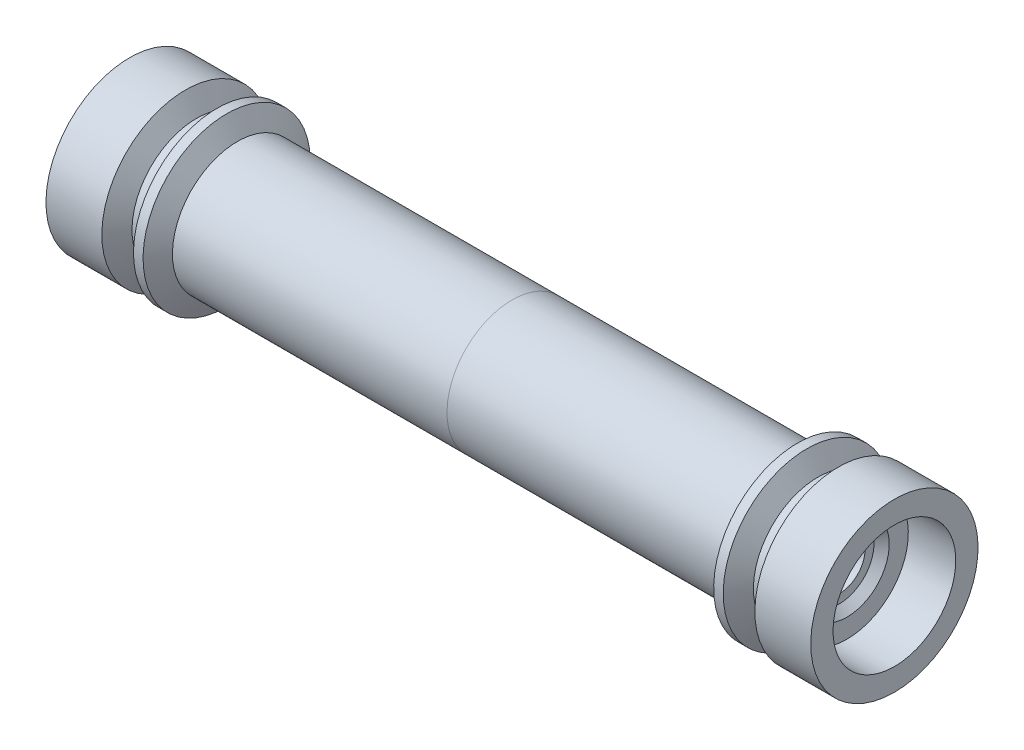
SolidWorks part; units mm, degrees
ref_plane "Front Plane" through (0, 0, 0) normal (0, 0, 1) x (1, 0, 0)
ref_plane "Top Plane" through (0, 0, 0) normal (0, 1, 0) x (1, 0, 0)
ref_plane "Right Plane" through (0, 0, 0) normal (1, 0, 0) x (0, 0, -1)
sketch "Sketch2" plane through (0, 0, 0) normal (0, 0, 1) x (1, 0, 0)
  line L0 (0, 0) -> (0, 28.4375) construction
  line L1 (-25.4, 4.075) -> (-22.25, 4.075) construction
  line L2 (-25.4, 4.075) -> (-25.4, -4.075) construction
  line L3 (-25.4, -4.075) -> (-22.25, -4.075) construction
  line L4 (-22.25, 4.075) -> (-22.25, -4.075) construction
  line L5 (-25.4, 4.075) -> (-22.25, -4.075) construction
  line L6 (-25.4, -4.075) -> (-22.25, 4.075) construction
  line L7 (22.25, 4.5) -> (41.3332, 4.5) construction
  line L8 (22.25, 4.5) -> (22.25, -4.5) construction
  line L9 (22.25, -4.5) -> (41.3332, -4.5) construction
  line L10 (41.3332, 4.5) -> (41.3332, -4.5) construction
  line L11 (22.25, 4.5) -> (41.3332, -4.5) construction
  line L12 (22.25, -4.5) -> (41.3332, 4.5) construction
  line L13 (-25.4, 0) -> (41.3332, 0) construction
  line L14 (-25.4, 5.5562) -> (-21.6882, 5.5562)
  line L21 (-18.2369, 4.318) -> (0, 4.318)
  line L22 (-25.4, 5.5562) -> (-25.4, 4.075)
  line L23 (-25.4, 4.075) -> (-22.25, 4.075)
  line L24 (-22.25, 4.075) -> (-22.25, 0)
  line L25 (-22.25, 0) -> (0, 0)
  line L26 (0, 0) -> (0, 4.318)
  line L27 (-30.6688, -5.5562) -> (-30.6688, 5.5562) construction
  line L28 (-21.6882, 5.5562) -> (-20.955, 4.2862)
  line L29 (-20.955, 4.2862) -> (-20.32, 4.2862)
  line L30 (-25.4, 5.5562) -> (25.4, 5.5562) construction
  line L31 (0, 1.6) -> (-12.5, 1.6)
  line L32 (-12.5, 1.6) -> (-14.1, 0)
  line L33 (-12.5, 1.6) -> (-12.5, -1.6) construction
  line L34 (-12.5, 1.6) -> (12.5, 1.6) construction
  line L35 (-22.25, 1.7145) -> (-15.575, 1.7145)
  line L36 (-15.575, 1.7145) -> (-15.575, 0)
  line L37 (-22.25, 2.805) -> (-21.742, 2.297)
  line L38 (-15.575, 1.7145) -> (-28.575, 1.7145) construction
  line L39 (-15.575, 1.7145) -> (-15.575, -1.7145) construction
  line L40 (-15.575, -1.7145) -> (-28.575, -1.7145) construction
  line L41 (-28.575, 1.7145) -> (-28.575, -1.7145) construction
  line L42 (-21.742, 2.297) -> (-21.742, 0)
  line L46 (-20.32, 4.2862) -> (-19.5868, 5.5562)
  line L47 (-19.5868, 5.5562) -> (-18.9518, 5.5562)
  line L48 (-18.9518, 5.5562) -> (-18.2369, 4.318)
  line L49 (-20.6375, 4.2862) -> (-20.6375, 8.7882) construction
  line L50 (-20.6375, 8.7882) -> (20.6375, 8.7882) construction
  point P0 (-23.825, 0)
  point P5 (31.7916, 0)
  point P27 (-30.6688, 0)
  point P29 (-12.5, 0)
  point P33 (0, 8.7882)
  point P36 (0, 1.6)
  point P48 (-15.575, 0)
  point P51 (0, 5.5562)
  dimension "D3" = 4.318
  dimension "D4" = 11.1125
  dimension "D5" = 8.15
  dimension "D6" = 60
  dimension "D7" = 0.635
  dimension "D8" = 60
  dimension "D9" = 41.275
  dimension "D10" = 1.27
  dimension "D11" = 50.8
  dimension "D12" = 0.635
  dimension "D13" = 45
  dimension "D14" = 25
  dimension "D15" = 3.2
  dimension "D16" = 3.429
  dimension "D17" = 3.175
  dimension "D18" = 1.27
  dimension "D19" = 0.508
  dimension "D20" = 45
  dimension "D21" = 13
  dimension "D22" = 3.15
revolve "Revolve1" add sketch "Sketch2" angle 360 about L13 region at (-12.3482, 3.069, 0)
mirror "Mirror1" about plane through (0, 0, 0) normal (1, 0, 0) of bodies 101
chamfer "Chamfer1" distance 0.508 angle 45 1 edges at (-25.4, -4.075, 0)
